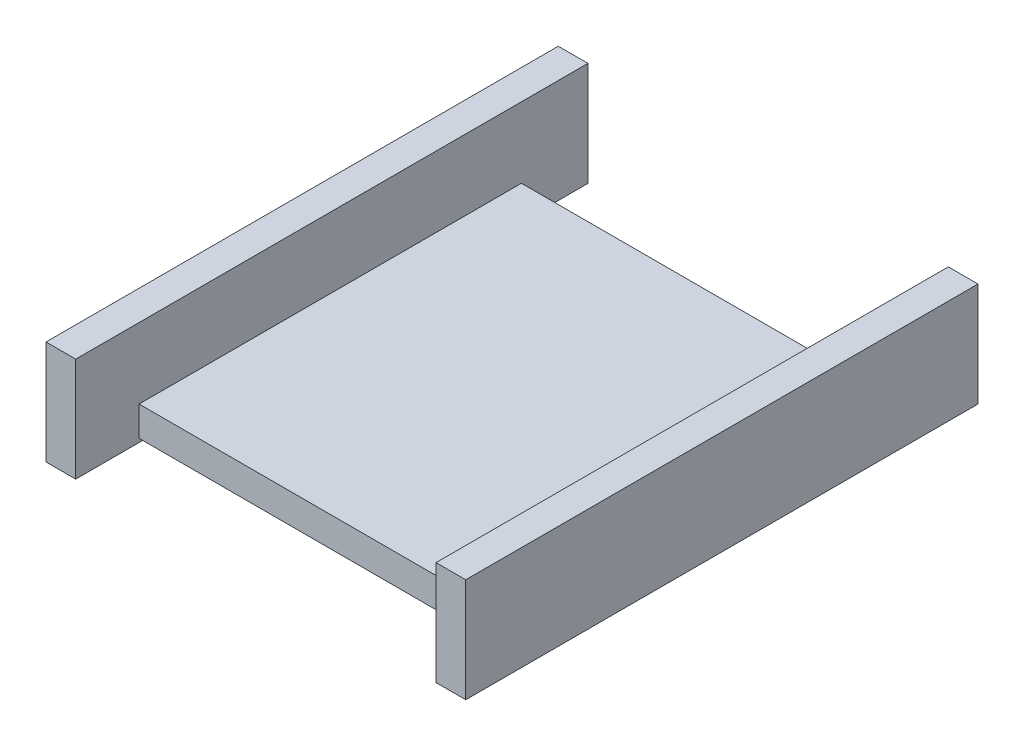
SolidWorks part; units mm, degrees
ref_plane "前视基准面" through (0, 0, 0) normal (0, 0, 1) x (1, 0, 0)
ref_plane "上视基准面" through (0, 0, 0) normal (0, 1, 0) x (1, 0, 0)
ref_plane "右视基准面" through (0, 0, 0) normal (1, 0, 0) x (0, 0, -1)
sketch "草图1" plane through (0, 0, 0) normal (1, 0, 0) x (0, 0, -1)
  line L1 (-69, 14) -> (69, 14)
  line L2 (-69, 14) -> (-69, -14)
  line L3 (-69, -14) -> (69, -14)
  line L4 (69, 14) -> (69, -14)
  line L5 (-69, 14) -> (69, -14) construction
  line L6 (-69, -14) -> (69, 14) construction
  point P0 (0, 0)
  dimension "D1" = 138
  dimension "D2" = 28
extrude "凸台-拉伸1" add sketch "草图1" along normal blind 8
sketch "草图2" plane through (0, 0, 0) normal (-1, 0, 0) x (0, 0, 1)
  line L0 (69, -14) -> (-69, -14) construction
  line L1 (-51, -6) -> (52, -6)
  line L2 (-51, -6) -> (-51, -14)
  line L3 (-51, -14) -> (52, -14)
  line L4 (52, -6) -> (52, -14)
  line L5 (-69, -14) -> (-69, 14) construction
  dimension "D1" = 18
  dimension "D2" = 103
  dimension "D3" = 8
extrude "凸台-拉伸2" add sketch "草图2" along normal blind 97
sketch "草图3" plane through (-97, 0, 0) normal (-1, 0, 0) x (0, 0, 1)
  line L1 (69.0702, -14.9897) -> (-68.9298, -14.9897)
  line L2 (69.0702, -14.9897) -> (69.0702, 13.0103)
  line L3 (69.0702, 13.0103) -> (-68.9298, 13.0103)
  line L4 (-68.9298, -14.9897) -> (-68.9298, 13.0103)
  dimension "D1" = 28
  dimension "D2" = 138
extrude "凸台-拉伸3" add sketch "草图3" along normal blind 8
